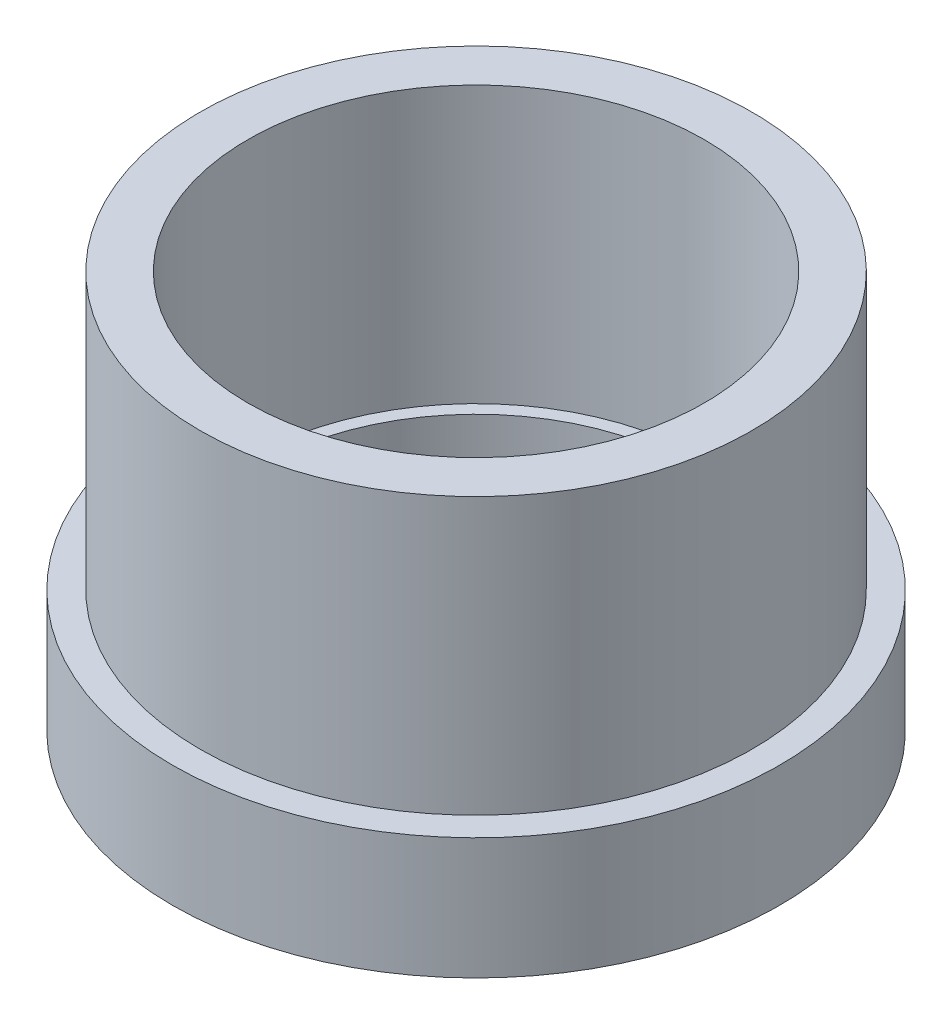
SolidWorks part; units mm, degrees
material "Custom Plastic"
ref_plane "Front Plane" through (0, 0, 0) normal (0, 0, 1) x (1, 0, 0)
ref_plane "Top Plane" through (0, 0, 0) normal (0, 1, 0) x (1, 0, 0)
ref_plane "Right Plane" through (0, 0, 0) normal (1, 0, 0) x (0, 0, -1)
sketch "Sketch1" plane through (0, 0, 0) normal (0, 0, 1) x (1, 0, 0)
  line L0 (39, 0) -> (39, 10)
  line L1 (0, 83.5208) -> (0, -98.2024) construction
  line L2 (39, 10) -> (55, 10)
  line L3 (55, 10) -> (55, -12)
  line L4 (55, -12) -> (41.5, -12)
  line L5 (41.5, -12) -> (41.5, 0)
  line L6 (41.5, 0) -> (39, 0)
  dimension "D1" = 39
  dimension "D2" = 55
  dimension "D3" = 41.5
  dimension "D4" = 22
  dimension "D5" = 10
  dimension "D6" = 0
revolve "Revolve1" add sketch "Sketch1" angle 360 about L1
sketch "Sketch3" plane through (0, -12, 0) normal (0, -1, 0) x (1, 0, 0)
  circle A0 centre (0, 48.25) radius 1.6
  circle A4 centre (48.25, 0) radius 1.6
  circle A5 centre (0, -48.25) radius 1.6
  circle A6 centre (-48.25, 0) radius 1.6
  point P12 (0, 0)
  point P13 (0, 0)
  dimension "D1" = 3.2
  dimension "D2" = 48.25
  dimension "D3" = 4
sketch "Sketch4" plane through (0, 10, 0) normal (0, 1, 0) x (1, 0, 0)
  circle A0 centre (0, 0) radius 41.35
  circle A1 centre (0, 0) radius 50
  dimension "D1" = 82.7
  dimension "D2" = 100
extrude "Boss-Extrude1" add sketch "Sketch4" along normal blind 50
extrude "Cut-Extrude1" cut sketch "Sketch3" against normal blind 10 contours A0 | A6 | A5 | A4
